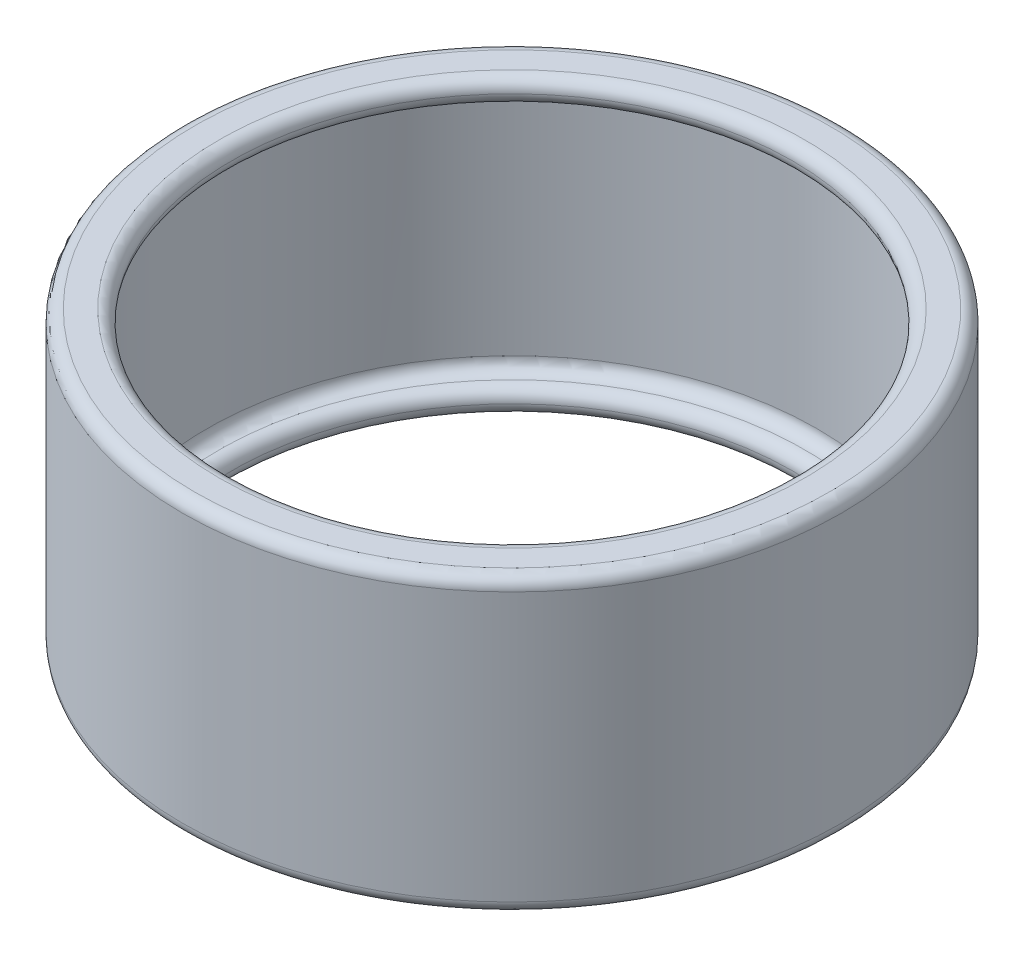
SolidWorks part; units mm, degrees
material "Alloy Steel"
ref_plane "Front Plane" through (0, 0, 0) normal (0, 0, 1) x (1, 0, 0)
ref_plane "Top Plane" through (0, 0, 0) normal (0, 1, 0) x (1, 0, 0)
ref_plane "Right Plane" through (0, 0, 0) normal (1, 0, 0) x (0, 0, -1)
sketch "Sketch3" plane through (0, 0, 0) normal (0, 0, 1) x (1, 0, 0)
  line L0 (0, 0) -> (0, 51.0181) construction
  line L1 (0, 0) -> (39.7342, 0) construction
  line L2 (27, -12) -> (27, 12)
  line L3 (27, 12) -> (23, 12)
  line L4 (23, 12) -> (23, 10)
  line L5 (23, 10) -> (25, 10)
  line L6 (25, 10) -> (25, -10)
  line L7 (23, -10) -> (25, -10)
  line L8 (23, -12) -> (23, -10)
  line L9 (27, -12) -> (23, -12)
  point P3 (25, 0)
  point P14 (27, 0)
  dimension "D1" = 25
  dimension "D2" = 12
  dimension "D3" = 10
  dimension "D4" = 2
  dimension "D5" = 4
revolve "Revolve1" add sketch "Sketch3" angle 360 about L0
fillet "Fillet1" radius 1 7 edges at (0, 10, -23) (0, 12, -23) (0, 12, -27) (0, -12, -23) (0, -12, -27) (0, -10, -25) (0, -10, -23)
